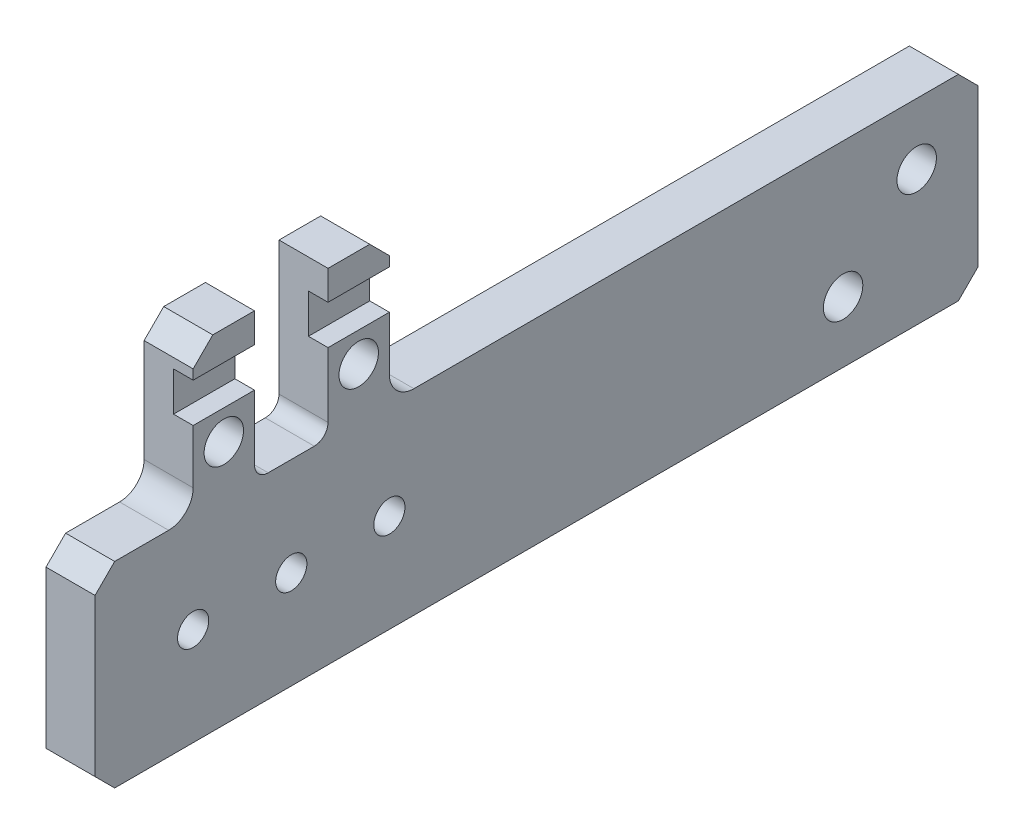
SolidWorks part; units mm, degrees
material "6061-T6 (SS)"
ref_plane "Front" through (0, 0, 0) normal (0, 0, 1) x (1, 0, 0)
ref_plane "Top" through (0, 0, 0) normal (0, 1, 0) x (1, 0, 0)
ref_plane "Right" through (0, 0, 0) normal (1, 0, 0) x (0, 0, -1)
sketch "Sketch1" plane through (0, 0, 0) normal (1, 0, 0) x (0, 0, -1)
  line L1 (0, 0) -> (114.3, 0)
  line L2 (0, 0) -> (0, 25.4)
  line L3 (0, 25.4) -> (9.525, 25.4)
  line L6 (114.3, 0) -> (114.3, 25.4)
  line L7 (38.1, 28.575) -> (38.1, 44.45)
  line L8 (38.1, 44.45) -> (30.1625, 44.45)
  line L9 (12.7, 44.45) -> (12.7, 28.575)
  line L10 (41.275, 25.4) -> (114.3, 25.4)
  line L11 (50.8, 25.4) -> (38.1, 44.45) construction
  line L12 (12.7, 44.45) -> (0, 25.4) construction
  line L14 (30.1625, 44.45) -> (30.1625, 27.178)
  line L15 (28.3845, 25.4) -> (22.4155, 25.4)
  line L16 (20.6375, 27.178) -> (20.6375, 44.45)
  line L17 (20.6375, 44.45) -> (12.7, 44.45)
  arc A0 (12.7, 28.575) -> (9.525, 25.4) centre (9.525, 28.575) cw
  arc A1 (38.1, 28.575) -> (41.275, 25.4) centre (41.275, 28.575) ccw
  arc A2 (22.4155, 25.4) -> (20.6375, 27.178) centre (22.4155, 27.178) cw
  arc A3 (30.1625, 27.178) -> (28.3845, 25.4) centre (28.3845, 27.178) cw
  point P14 (38.1, 25.4)
  dimension "D3" = 50.8
  dimension "D6" = 3.175
  dimension "D8" = 1.778
  dimension "D1" = 25.4
  dimension "D2" = 19.05
  dimension "D4" = 114.3
  dimension "D5" = 25.4
  dimension "D7" = 9.525
extrude "Boss-Extrude1" add sketch "Sketch1" along normal blind 6.35
hole_wizard "#10-32 Tapped Hole1" positions "Sketch2" profile "Sketch3" tap size "#10-32" standard "ANSI Inch" end condition through all
sketch "Sketch2" plane through (6.35, 0, 0) normal (1, 0, 0) x (0, 0, -1)
  line L0 (0, 0) -> (12.7, 12.7) construction
  line L1 (12.7, 12.7) -> (25.4, 12.7) construction
  line L2 (25.4, 12.7) -> (38.1, 12.7) construction
  line L3 (38.1, 12.7) -> (50.8, 25.4) construction
  line L4 (9.525, 25.4) -> (0, 25.4) construction
  line L6 (0, 25.4) -> (0, 0) construction
  point P0 (12.7, 12.7)
  point P2 (25.4, 12.7)
  point P4 (38.1, 12.7)
  dimension "D1" = 50.8
  dimension "D2" = 12.7
sketch "Sketch3" plane through (6.35, 12.7, -12.7) normal (0, 1, 0) x (0, 0, -1)
  line L0 (0, 0) -> (0, 6.35)
  line L1 (0, 6.35) -> (2.0193, 6.35)
  line L2 (2.0193, 6.35) -> (2.0193, 0)
  line L5 (2.0193, 0) -> (0, 0)
  line L11 (0, -6.35) -> (0, 107.95) construction
  dimension "Thru Tap Drill Dia." = 4.0386
  dimension "Thru Tap Drill Depth" = 6.35
cosmetic thread "Hole Thread1" parameters "D2"=4.826
cosmetic thread "Hole Thread2" parameters "D2"=4.826
cosmetic thread "Hole Thread3" parameters "D2"=4.826
hole_wizard "#10 Clearance Hole1" positions "Sketch4" profile "Sketch5" hole size "#10" standard "ANSI Inch" end condition through all
sketch "Sketch4" plane through (6.35, 0, 0) normal (1, 0, 0) x (0, 0, -1)
  line L0 (88.9, 0) -> (96.8375, 7.9375) construction
  line L1 (0, 0) -> (114.3, 0) construction
  line L2 (96.8375, 7.9375) -> (106.3625, 17.4625) construction
  line L3 (106.3625, 17.4625) -> (114.3, 25.4) construction
  line L5 (114.3, 0) -> (114.3, 25.4) construction
  line L6 (20.6375, 44.45) -> (16.6688, 31.75) construction
  line L7 (16.6688, 31.75) -> (12.7, 44.45) construction
  line L10 (30.1625, 44.45) -> (34.1313, 31.75) construction
  line L11 (34.1313, 31.75) -> (38.1, 44.45) construction
  line L13 (9.525, 25.4) -> (0, 25.4) construction
  point P13 (106.3625, 17.4625)
  point P15 (96.8375, 7.9375)
  point P37 (34.1313, 31.75)
  point P39 (16.6688, 31.75)
  dimension "D1" = 25.4
  dimension "D2" = 9.525
  dimension "D3" = 6.35
sketch "Sketch5" plane through (6.35, 17.4625, -106.3625) normal (0, 1, 0) x (0, 0, -1)
  line L0 (0, 0) -> (0, 6.35)
  line L1 (0, 6.35) -> (2.5527, 6.35)
  line L2 (2.5527, 6.35) -> (2.5527, 0)
  line L5 (2.5527, 0) -> (0, 0)
  line L11 (0, -6.35) -> (0, 107.95) construction
  dimension "Thru Hole Dia." = 5.1054
  dimension "Thru Hole Depth" = 6.35
sketch "Sketch6" plane through (6.35, 0, 0) normal (1, 0, 0) x (0, 0, -1)
  line L0 (12.7, 44.45) -> (12.7, 28.575) construction
  line L1 (12.7, 40.64) -> (38.1, 40.64)
  line L2 (12.7, 40.64) -> (12.7, 35.56)
  line L3 (12.7, 35.56) -> (38.1, 35.56)
  line L4 (38.1, 40.64) -> (38.1, 35.56)
  line L5 (38.1, 28.575) -> (38.1, 44.45) construction
  line L6 (9.525, 25.4) -> (0, 25.4) construction
  point P8 (12.7, 38.1)
  dimension "D1" = 5.08
  dimension "D2" = 12.7
extrude "Cut-Extrude1" cut sketch "Sketch6" against normal blind 2.54
chamfer "Chamfer1" distance 2.54 angle 45 6 edges at (3.175, 44.45, -38.1) (3.175, 44.45, -12.7) (3.175, 25.4, -114.3) (3.175, 0, -114.3) (3.175, 0, 0) (3.175, 25.4, 0)
